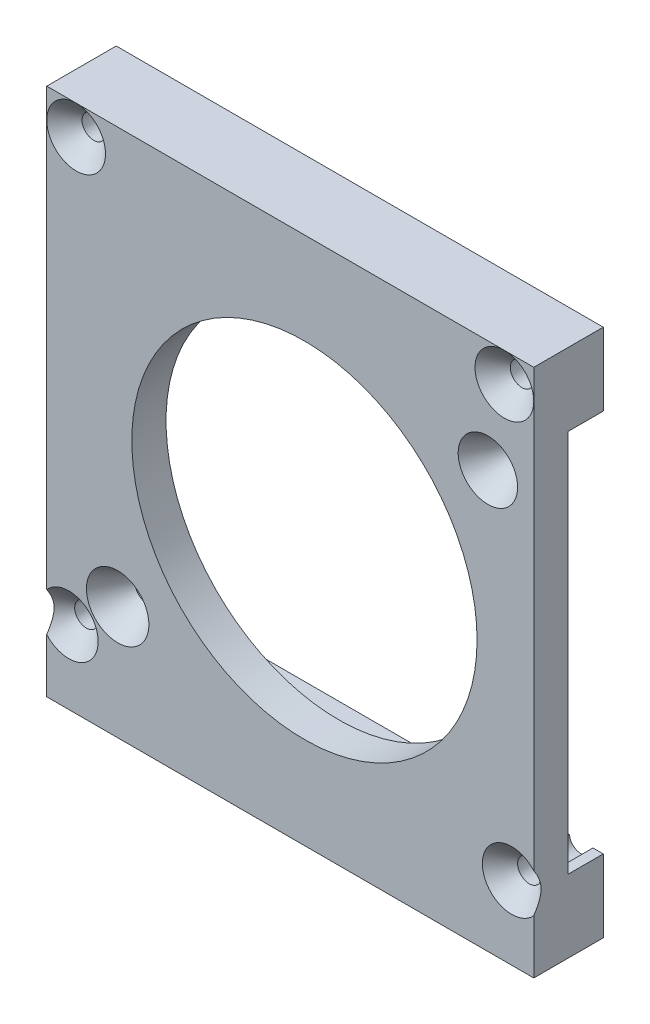
SolidWorks part; units mm, degrees
ref_plane "Front Plane" through (0, 0, 0) normal (0, 0, 1) x (1, 0, 0)
ref_plane "Top Plane" through (0, 0, 0) normal (0, 1, 0) x (1, 0, 0)
ref_plane "Right Plane" through (0, 0, 0) normal (1, 0, 0) x (0, 0, -1)
sketch "Sketch1" plane through (0, 0, 0) normal (0, 0, 1) x (1, 0, 0)
  line L0 (12.0169, 13.05) -> (16.575, 18) construction
  line L1 (-16.575, -18) -> (16.575, -18)
  line L2 (-16.575, -18) -> (-16.575, 18)
  line L3 (-16.575, 18) -> (16.575, 18)
  line L4 (16.575, -18) -> (16.575, -13.05)
  line L5 (-16.575, -18) -> (-12.0169, -13.05) construction
  line L6 (-16.575, 18) -> (-12.0169, 13.05) construction
  line L7 (16.575, 13.05) -> (16.575, 18)
  line L8 (-14.975, -13.05) -> (16.575, -13.05)
  line L9 (-14.975, -13.05) -> (-14.975, 13.05)
  line L10 (-14.975, 13.05) -> (16.575, 13.05)
  line L12 (12.0169, -13.05) -> (16.575, -18) construction
  point P0 (0, 0)
  dimension "D1" = 33.15
  dimension "D2" = 36
  dimension "D3" = 26.1
  dimension "D4" = 1.6
extrude "Boss-Extrude1" add sketch "Sketch1" along normal blind 2.4
sketch "Sketch2" plane through (0, 0, 2.4) normal (0, 0, 1) x (1, 0, 0)
  line L0 (-14.975, -13.05) -> (-14.975, 13.05) construction
  line L1 (-16.575, 18) -> (16.575, 18)
  line L2 (-16.575, 18) -> (-16.575, -18)
  line L3 (-16.575, -18) -> (16.575, -18)
  line L4 (16.575, 18) -> (16.575, -18)
  line L5 (-12.675, -10.2729) -> (-12.675, -9.8377) construction
  line L6 (-10.785, 0) -> (-10.785, 5.0525) construction
  line L9 (-11.7479, -11.2) -> (-10.1563, -11.2)
  line L10 (13.453, 11.2) -> (11.4356, 11.2) construction
  line L11 (14.275, 10.378) -> (14.275, 10.3258) construction
  line L12 (-14.975, 13.05) -> (16.575, 13.05) construction
  line L13 (16.575, -13.05) -> (-14.975, -13.05) construction
  circle A0 centre (0.965, 0) radius 11.75
  circle A1 centre (13.453, 10.378) radius 0.822
  circle A2 centre (-11.7479, -10.2729) radius 0.9271
  dimension "D1" = 23.5
  dimension "D2" = 4.19
  dimension "D3" = 2.3
  dimension "D4" = 2.3
  dimension "D5" = 1.85
  dimension "D6" = 1.85
extrude "Boss-Extrude2" add sketch "Sketch2" along normal blind 2.33
chamfer "Chamfer1" distance 1.2 angle 60 2 edges at (-10.8208, -10.2729, 4.73) (14.275, 10.378, 4.73) first distance on face at (0, 0, 4.73)
sketch "Sketch3" plane through (0, 0, 4.73) normal (0, 0, 1) x (1, 0, 0)
  line L0 (0, 0) -> (0, 7.6755) construction
  line L1 (16.575, 18) -> (-16.575, 18) construction
  line L2 (-16.575, 18) -> (-16.575, -18) construction
  line L3 (-16.575, -18) -> (16.575, -18) construction
  circle A0 centre (-14.575, 16) radius 0.8
  circle A1 centre (14.575, 16) radius 0.8
  circle A2 centre (-15.075, -13) radius 0.8
  circle A3 centre (15.075, -13) radius 0.8
  point P7 (0, 0)
  point P15 (-14.8955, -17.5774)
  dimension "D2" = 1.6
  dimension "D4" = 1.6
  dimension "D1" = 2
  dimension "D3" = 2
  dimension "D5" = 1.5
  dimension "D6" = 5
extrude "Cut-Extrude1" cut sketch "Sketch3" against normal blind 5.8
chamfer "Chamfer2" distance 1.2 angle 45 4 edges at (-14.275, -13, 4.73) (14.275, -13, 4.73) (13.775, 16, 4.73) (-13.775, 16, 4.73)
